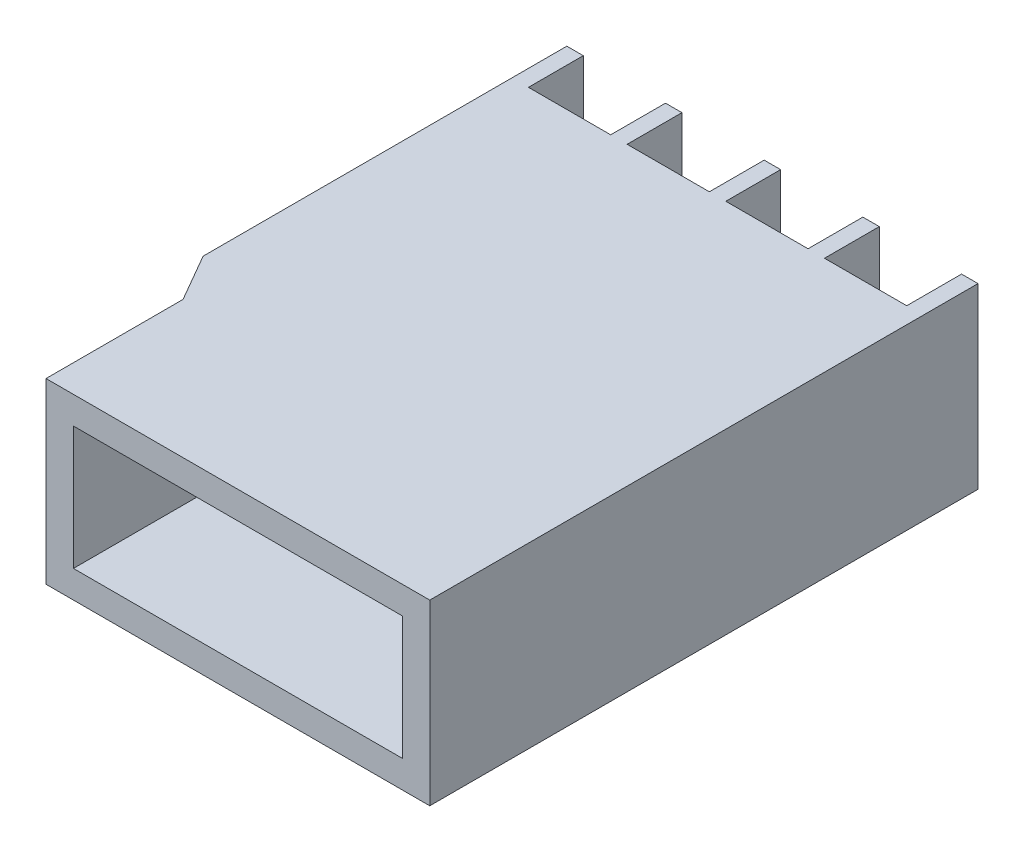
SolidWorks part; units mm, degrees
ref_plane "Front Plane" through (0, 0, 0) normal (0, 0, 1) x (1, 0, 0)
ref_plane "Top Plane" through (0, 0, 0) normal (0, 1, 0) x (1, 0, 0)
ref_plane "Right Plane" through (0, 0, 0) normal (1, 0, 0) x (0, 0, -1)
sketch "Sketch3" plane through (0, 0, 0) normal (0, 1, 0) x (1, 0, 0)
  line L0 (-75, 80) -> (75, 80) construction
  line L1 (75, -100) -> (-75, -100)
  line L2 (75, -100) -> (75, 100)
  line L3 (75, 100) -> (69, 100)
  line L4 (-75, -100) -> (-75, 100)
  line L5 (75, -100) -> (-75, 100) construction
  line L6 (75, 100) -> (-75, -100) construction
  line L8 (-69, 100) -> (-69, 80)
  line L9 (-69, 80) -> (-39, 80)
  line L10 (-39, 100) -> (-39, 80)
  line L11 (-33, 100) -> (-33, 80)
  line L13 (-3, 100) -> (-3, 80)
  line L14 (-33, 80) -> (-3, 80)
  line L15 (3, 100) -> (3, 80)
  line L17 (33, 100) -> (33, 80)
  line L18 (3, 80) -> (33, 80)
  line L19 (39, 100) -> (39, 80)
  line L21 (69, 100) -> (69, 80)
  line L22 (39, 80) -> (69, 80)
  line L23 (-75, -32.6795) -> (-65, -50)
  line L24 (-65, -50) -> (-65, -100)
  line L25 (-65, -100) -> (-75, -100)
  line L26 (-69, 100) -> (-75, 100)
  line L27 (-33, 100) -> (-39, 100)
  line L28 (3, 100) -> (-3, 100)
  line L29 (39, 100) -> (33, 100)
  point P0 (0, 0)
  dimension "D1" = 150
  dimension "D2" = 200
  dimension "D3" = 6
  dimension "D4" = 30
  dimension "D5" = 20
  dimension "D7" = 6
  dimension "D9" = 50
  dimension "D10" = 30
  dimension "D11" = 10
  dimension "D6" = 4
extrude "Boss-Extrude2" add sketch "Sketch3" against normal blind 65 contours L19 L29 L17 L18 L15 L28 L13 L14 L11 L27 L10 L9 L8 L26 L4 L23 L24 L1 L2 L3 L21 L22 region at (1.5254, 0, 6.466)
shell "Shell1" thickness 10 removed face at (5, -32.5, 100)
